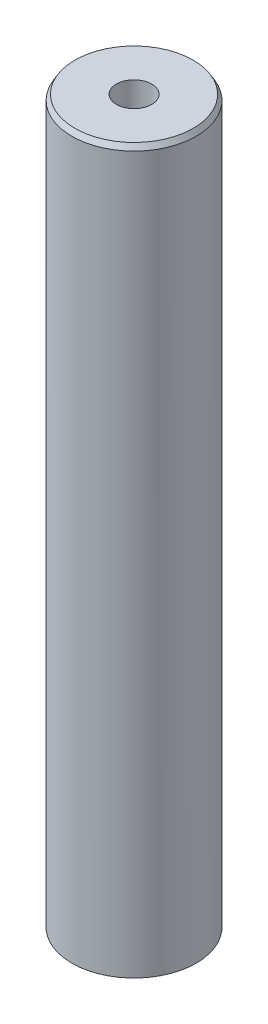
SolidWorks part; units mm, degrees
ref_plane "Front Plane" through (0, 0, 0) normal (0, 0, 1) x (1, 0, 0)
ref_plane "Top Plane" through (0, 0, 0) normal (0, 1, 0) x (1, 0, 0)
ref_plane "Right Plane" through (0, 0, 0) normal (1, 0, 0) x (0, 0, -1)
sketch "Sketch1" plane through (0, 0, 0) normal (0, 1, 0) x (1, 0, 0)
  circle A0 centre (0, 0) radius 22.5
  dimension "SHAFT_OD" = 45
extrude "Boss-Extrude1" add sketch "Sketch1" along normal blind 262.076
sketch "Sketch2" plane through (0, 0, 0) normal (0, 1, 0) x (1, 0, 0)
  circle A0 centre (0, 0) radius 6.3951
  dimension "BORE_D" = 12.7902
extrude "Cut-Extrude1" cut sketch "Sketch2" along normal through all
chamfer "Chamfer1" distance 1.925 angle 30 2 edges at (0, 262.076, 22.5) (0, 0, 22.5) first distance on face at (0, 262.076, 22.5) first distance on face at (0, 0, 6.3951)
